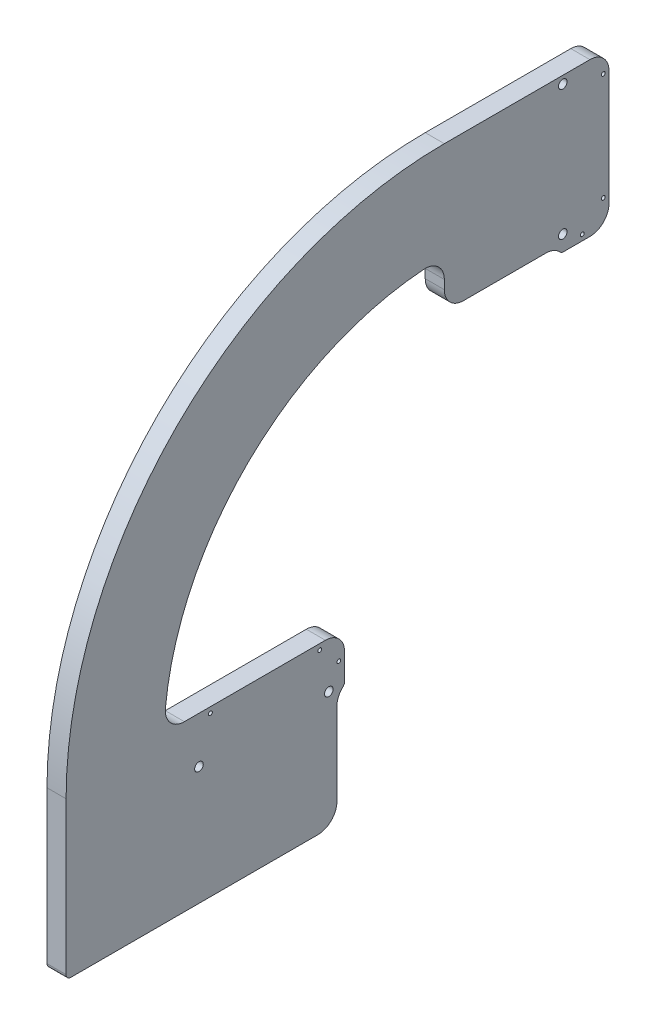
SolidWorks part; units mm, degrees
ref_plane "Front Plane" through (0, 0, 0) normal (0, 0, 1) x (1, 0, 0)
ref_plane "Top Plane" through (0, 0, 0) normal (0, 1, 0) x (1, 0, 0)
ref_plane "Right Plane" through (0, 0, 0) normal (1, 0, 0) x (0, 0, -1)
sketch "Sketch2" plane through (10, 0, 0) normal (-1, 0, 0) x (0, 0, 1)
  line L0 (27.834, 141.152) -> (27.834, 124.6391) construction
  line L1 (-54.366, 160.2654) -> (27.834, 160.2654) construction
  line L2 (-54.366, 160.2654) -> (-54.366, 84.0654) construction
  line L3 (-54.366, 84.0654) -> (27.834, 84.0654) construction
  line L4 (27.834, 160.2654) -> (27.834, 84.0654) construction
  line L5 (-25.1737, 84.0654) -> (-51.666, 84.0654) construction
  line L6 (-54.366, 86.7654) -> (-54.366, 157.7654) construction
  line L7 (-51.666, 160.2654) -> (6.8746, 160.2654) construction
  line L8 (160.284, -40.433) -> (160.284, -98.9737) construction
  line L9 (84.084, -37.733) -> (160.284, -37.733) construction
  line L10 (84.084, -37.733) -> (84.084, -119.933) construction
  line L11 (84.084, -119.933) -> (160.284, -119.933) construction
  line L12 (160.284, -37.733) -> (160.284, -119.933) construction
  line L13 (86.784, -37.733) -> (157.784, -37.733) construction
  line L14 (84.084, -66.9254) -> (84.084, -40.433) construction
  line L15 (141.1706, -119.933) -> (124.6576, -119.933) construction
  point P12 (-34.166, 156.2654)
  point P13 (-34.166, 88.2654)
  point P17 (88.284, -57.933)
  point P18 (156.284, -57.933)
sketch "Sketch1" plane through (0, 0, 0) normal (1, 0, 0) x (0, 0, -1)
  line L0 (-27.834, 109.0654) -> (-27.834, 160.2654) construction
  line L1 (-225.8324, -37.733) -> (-174.6324, -37.733) construction
  line L2 (-27.834, 109.0654) -> (-27.834, 84.0654)
  line L3 (-27.834, 84.0654) -> (54.366, 84.0654) construction
  line L4 (54.366, 84.0654) -> (54.366, 160.2654) construction
  line L5 (54.366, 160.2654) -> (-27.834, 160.2654)
  line L6 (-225.8324, -37.733) -> (-225.8324, -119.933)
  line L7 (-225.8324, -119.933) -> (-84.084, -119.933)
  line L8 (-84.084, -119.933) -> (-84.084, -37.733) construction
  line L9 (-84.084, -37.733) -> (-174.6324, -37.733) construction
  line L11 (-84.084, -37.733) -> (-84.084, -119.933) construction
  line L12 (54.366, 84.0654) -> (-27.834, 84.0654) construction
  line L13 (54.366, 160.2654) -> (54.366, 84.0654) construction
  line L14 (-84.084, -37.733) -> (-160.284, -37.733) construction
  line L15 (-27.834, 160.2654) -> (-27.834, 84.0654) construction
  line L16 (-84.084, -119.933) -> (-160.284, -119.933) construction
  line L17 (54.366, 160.2654) -> (-27.834, 160.2654) construction
  line L19 (58.366, 80.0654) -> (58.366, 160.2654)
  line L20 (58.366, 160.2654) -> (54.366, 160.2654)
  line L21 (-80.084, -33.733) -> (-174.5779, -33.733)
  line L22 (-80.084, -58.733) -> (-80.084, -33.733)
  line L23 (-80.084, -58.733) -> (-84.084, -58.733)
  line L24 (-84.084, -58.733) -> (-84.084, -119.933)
  line L25 (58.366, 80.0654) -> (33.366, 80.0654)
  line L26 (33.366, 80.0654) -> (33.366, 84.0654)
  line L27 (33.366, 84.0654) -> (-27.834, 84.0654)
  arc A2 (-27.834, 160.2654) -> (-225.8324, -37.733) centre (-27.834, -37.733) ccw
  arc A3 (-174.6324, -37.733) -> (-27.834, 109.0654) centre (-27.834, -37.733) cw construction
  arc A4 (-174.5779, -33.733) -> (-27.834, 109.0654) centre (-27.834, -37.733) cw
  dimension "D1" = 4
  dimension "D3" = 25
  dimension "D4" = 25
  dimension "D5" = 4
  dimension "D6" = 4
extrude "Boss-Extrude1" add sketch "Sketch1" along normal blind 10
hole_wizard "M4 Clearance Hole1" positions "Sketch3" profile "Sketch4" hole size "M4" standard "ANSI Metric" end condition through all
sketch "Sketch3" plane through (10, 0, 0) normal (1, 0, 0) x (0, 0, -1)
  point P0 (-156.284, -57.933)
  point P3 (-88.284, -57.933)
  point P6 (34.166, 156.2654)
  point P8 (34.166, 88.2654)
sketch "Sketch4" plane through (10, -57.933, 156.284) normal (0, 1, 0) x (0, 0, -1)
  line L0 (0, 0) -> (0, 10)
  line L1 (0, 10) -> (2.25, 10)
  line L2 (2.25, 10) -> (2.25, 0)
  line L5 (2.25, 0) -> (0, 0)
  line L11 (0, -6.35) -> (0, 107.95) construction
  dimension "Thru Hole Dia." = 4.5
  dimension "Thru Hole Depth" = 10
hole_wizard "Ø2.0mm Dowel Hole1" positions "Sketch5" profile "Sketch6" hole size "Ø2.0" standard "ISO" end condition through all
sketch "Sketch5" plane through (10, 0, 0) normal (1, 0, 0) x (0, 0, -1)
  line L1 (55.366, 150.2654) -> (55.366, 94.0654) construction
  line L2 (55.366, 94.0654) -> (55.366, 83.0654) construction
  line L3 (55.366, 83.0654) -> (44.366, 83.0654) construction
  line L5 (54.366, 160.2654) -> (54.366, 84.0654) construction
  line L6 (54.366, 84.0654) -> (-27.834, 84.0654) construction
  line L7 (58.366, 160.2654) -> (-27.834, 160.2654) construction
  line L8 (-150.284, -36.733) -> (-93.084, -36.733) construction
  line L9 (-93.084, -36.733) -> (-83.084, -36.733) construction
  line L10 (-83.084, -36.733) -> (-83.084, -46.733) construction
  line L12 (-84.084, -37.733) -> (-160.284, -37.733) construction
  line L13 (-84.084, -37.733) -> (-84.084, -119.933) construction
  line L14 (-160.284, -37.733) -> (-160.284, -119.933) construction
  point P0 (44.366, 83.0654)
  point P2 (55.366, 94.0654)
  point P4 (55.366, 150.2654)
  point P6 (-150.284, -36.733)
  point P8 (-93.084, -36.733)
  point P10 (-83.084, -46.733)
  point P41 (0, 0)
  point P42 (0, 0)
  point P43 (-83.084, -48.6883)
  point P44 (-83.084, -48.6883)
  dimension "D1" = 1
  dimension "D2" = 1
  dimension "D3" = 10
  dimension "D4" = 10
  dimension "D5" = 10
  dimension "D6" = 1
  dimension "D7" = 1
  dimension "D8" = 10
  dimension "D9" = 10
  dimension "D10" = 10
sketch "Sketch6" plane through (10, 83.0654, -44.366) normal (0, 1, 0) x (0, 0, -1)
  line L0 (0, 0) -> (0, 10)
  line L1 (0, 10) -> (1, 10)
  line L2 (1, 10) -> (1, 0)
  line L5 (1, 0) -> (0, 0)
  line L11 (0, -6.35) -> (0, 107.95) construction
  dimension "Thru Hole Dia." = 2
  dimension "Thru Hole Depth" = 10
fillet "Fillet1" radius 10 9 edges at (5, -58.733, 84.084) (5, 84.0654, -33.366) (5, -119.933, 84.084) (5, -33.733, 80.084) (5, -33.733, 174.5779) (5, 109.0654, 27.834) (5, 84.0654, 27.834) (5, 160.2654, -58.366) (5, 80.0654, -58.366)
fillet "Fillet2" radius 2.5 3 edges at (5, -119.933, 225.8324) (5, 80.0654, -33.366) (5, -58.733, 80.084)
